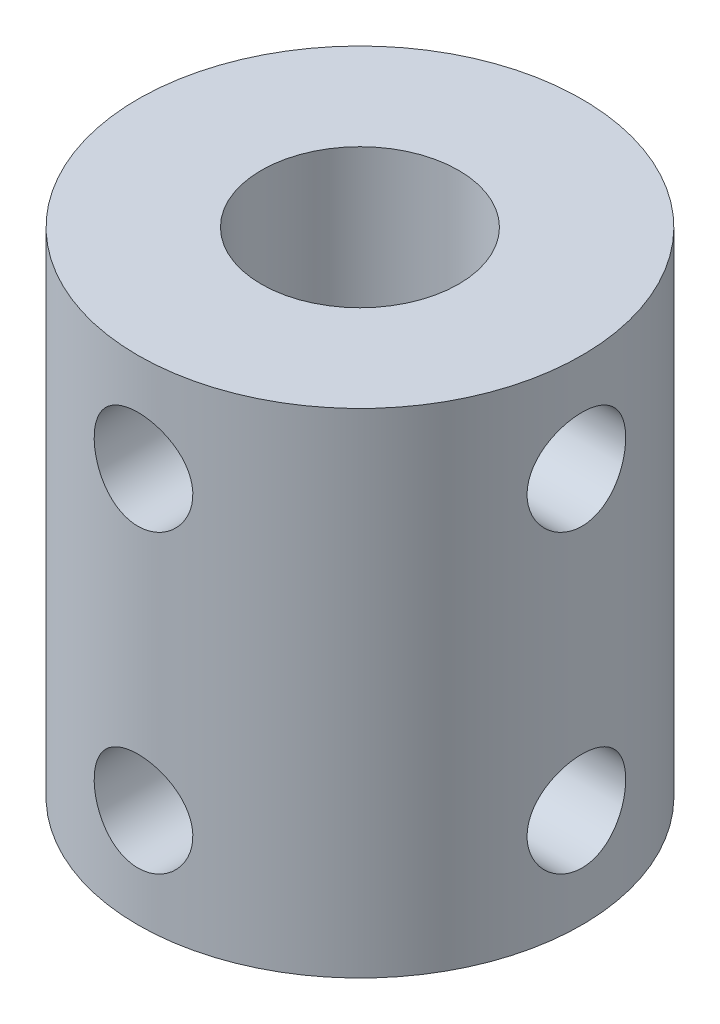
SolidWorks part; units mm, degrees
ref_plane "Front Plane" through (0, 0, 0) normal (0, 0, 1) x (1, 0, 0)
ref_plane "Top Plane" through (0, 0, 0) normal (0, 1, 0) x (1, 0, 0)
ref_plane "Right Plane" through (0, 0, 0) normal (1, 0, 0) x (0, 0, -1)
sketch "Sketch1" plane through (0, 0, 0) normal (0, 1, 0) x (1, 0, 0)
  circle A0 centre (0, 0) radius 4.5
  circle A1 centre (0, 0) radius 2
  dimension "D1" = 9
  dimension "D2" = 4
extrude "Boss-Extrude1" add sketch "Sketch1" along normal blind 10
ref_axis "Axis1" through (0, 10, 0) along (0, -1, 0)
ref_plane "Plane1" through (0, 0, 0) normal (-0.7071, 0, 0.7071) x (0, -1, 0)
sketch "Sketch2" plane through (0, 0, 0) normal (0, 0, 1) x (1, 0, 0)
  line L0 (0, -4.95) -> (0, 4.95) construction
  line L1 (4.5, 10) -> (-4.5, 10) construction
  line L2 (4.95, 0) -> (-4.95, 0) construction
  circle A0 centre (0, 8) radius 1
  circle A1 centre (0, 2) radius 1
  dimension "D1" = 2
  dimension "D2" = 2
  dimension "D3" = 2
  dimension "D4" = 2
extrude "Cut-Extrude1" cut sketch "Sketch2" along normal through all
mirror "Mirror1" about plane through (0, 0, 0) normal (-0.7071, 0, 0.7071) of "Cut-Extrude1"
